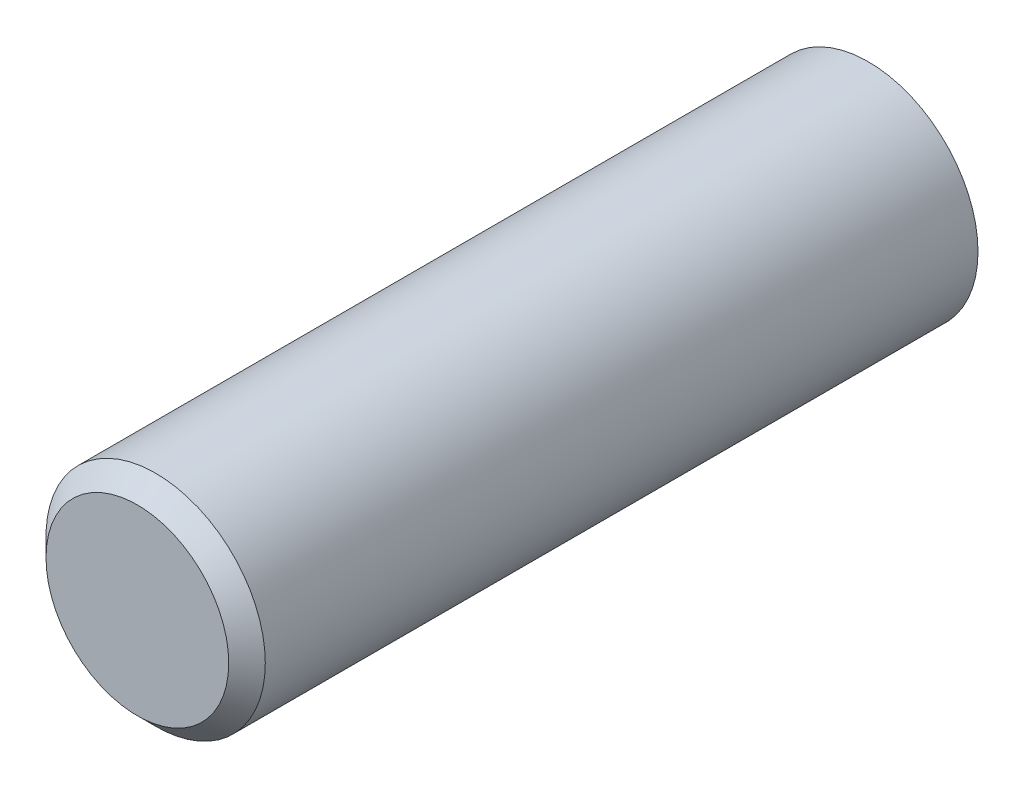
SolidWorks part; units mm, degrees
ref_plane "Front" through (0, 0, 0) normal (0, 0, 1) x (1, 0, 0)
ref_plane "Top" through (0, 0, 0) normal (0, 1, 0) x (1, 0, 0)
ref_plane "Right" through (0, 0, 0) normal (1, 0, 0) x (0, 0, -1)
sketch "Esquisse1" plane through (0, 0, 0) normal (0, 0, 1) x (1, 0, 0)
  circle A0 centre (0, 0) radius 3
  dimension "D1" = 6
extrude "Boss.-Extru.1" add sketch "Esquisse1" along normal blind 20
chamfer "Chanfrein1" distance 0.5 angle 45 1 edges at (3, 0, 20)
